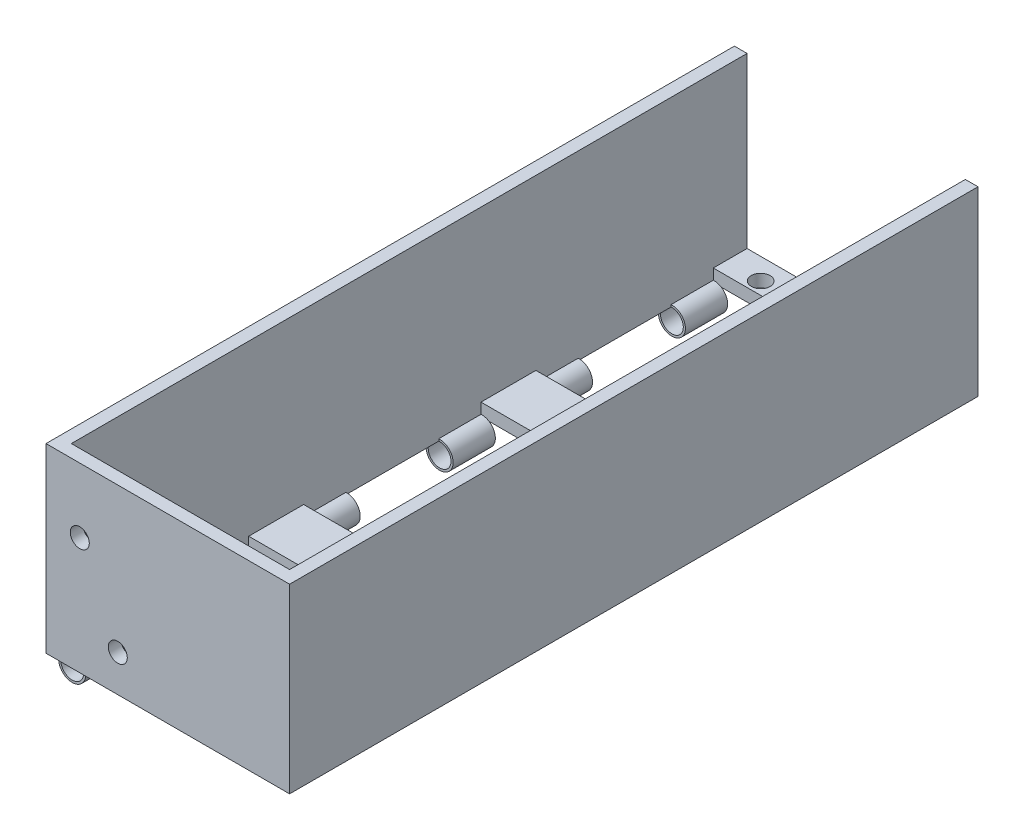
SolidWorks part; units mm, degrees
ref_plane "Front Plane" through (0, 0, 0) normal (0, 0, 1) x (1, 0, 0)
ref_plane "Top Plane" through (0, 0, 0) normal (0, 1, 0) x (1, 0, 0)
ref_plane "Right Plane" through (0, 0, 0) normal (1, 0, 0) x (0, 0, -1)
sketch "Sketch1" plane through (0, 0, 0) normal (0, 0, 1) x (1, 0, 0)
  line L0 (0, 0) -> (0, -10)
  line L1 (0, -10) -> (0, -40)
  line L2 (0, -40) -> (51.6786, -40)
  line L5 (-3, 0) -> (-3, -10)
  line L6 (-3, -10) -> (-3, -43)
  line L7 (-3, -43) -> (54.6786, -43)
  line L10 (-3, 0) -> (0, 0)
  line L12 (51.6786, -40) -> (51.6786, 0)
  line L13 (51.6786, -40) -> (51.6786, 37.6119) construction
  line L14 (51.6786, 37.6119) -> (67.0297, -2.1736) construction
  line L15 (54.6786, -43) -> (54.6786, 21.503) construction
  line L16 (54.6786, 21.503) -> (64.2308, -3.2535) construction
  line L17 (51.6786, 0) -> (54.6786, 0)
  line L18 (54.6786, 0) -> (54.6786, -43)
  dimension "D2" = 10
  dimension "D3" = 30
  dimension "D5" = 3
  dimension "D1" = 3
extrude "Boss-Extrude1" add sketch "Sketch1" along normal blind 160
sketch "Sketch2" plane through (0, 0, 0) normal (0, 1, 0) x (1, 0, 0)
  line L0 (51.6786, -160) -> (0, -160) construction
  line L1 (49, -8) -> (0, -8)
  line L2 (49, -8) -> (49, -50)
  line L3 (49, -50) -> (0, -50)
  line L4 (0, -8) -> (0, -50)
  line L5 (49, -63) -> (0, -63)
  line L6 (49, -63) -> (49, -105)
  line L7 (49, -105) -> (0, -105)
  line L8 (0, -63) -> (0, -105)
  line L9 (49, -118) -> (0, -118)
  line L10 (49, -118) -> (49, -160)
  line L11 (49, -160) -> (0, -160)
  line L12 (0, -118) -> (0, -160)
  line L13 (0, -160) -> (0, 0) construction
  dimension "D1" = 42
  dimension "D2" = 13
  dimension "D3" = 42
  dimension "D4" = 13
  dimension "D5" = 42
  dimension "D6" = 49
extrude "Cut-Extrude1" cut sketch "Sketch2" against normal through all
sketch "Sketch3" plane through (0, 0, 160) normal (0, 0, 1) x (1, 0, 0)
  line L0 (-3, 0) -> (54.6786, 0)
  line L1 (54.6786, 0) -> (54.6786, -43)
  line L2 (54.6786, -43) -> (0, -43)
  line L10 (0, 0) -> (-3, 0)
  line L11 (-3, 0) -> (-3, -43)
  line L13 (-3, -43) -> (0, -43)
  line L18 (0, -43) -> (0, 0)
  line L21 (-3, 0) -> (-3, -43)
  line L23 (-3, -43) -> (0, -43)
  dimension "D1" = 0
extrude "Boss-Extrude2" add sketch "Sketch3" along normal blind 3
sketch "Sketch4" plane through (0, 0, 163) normal (0, 0, 1) x (1, 0, 0)
  circle A0 centre (14, -34.2995) radius 2.25 construction
  circle A1 centre (5, -15.3106) radius 2.25 construction
  circle A2 centre (14, -34.2995) radius 2.25
  circle A3 centre (5, -15.3106) radius 2.25
extrude "Cut-Extrude2" cut sketch "Sketch4" against normal up to next
sketch "Sketch5" plane through (0, -40, 0) normal (0, 1, 0) x (1, 0, 0)
  line L14 (49, -8) -> (49, -50)
  line L15 (49, -50) -> (0, -50)
  line L16 (0, -50) -> (0, -63)
  line L17 (0, -63) -> (49, -63)
  line L18 (49, -63) -> (49, -105)
  line L19 (49, -105) -> (0, -105)
  line L20 (0, -105) -> (0, -118)
  line L21 (0, -118) -> (49, -118)
  line L22 (49, -118) -> (49, -160)
  line L23 (49, -160) -> (51.6786, -160)
  line L24 (51.6786, -160) -> (51.6786, 0)
  line L25 (51.6786, 0) -> (0, 0)
  line L26 (0, 0) -> (0, -8)
  line L27 (0, -8) -> (49, -8)
  line L28 (49, -8) -> (49, -50)
  line L29 (49, -50) -> (0, -50)
  line L30 (0, -50) -> (0, -63)
  line L31 (0, -63) -> (49, -63)
  line L32 (49, -63) -> (49, -105)
  line L33 (49, -105) -> (0, -105)
  line L34 (0, -105) -> (0, -118)
  line L35 (0, -118) -> (49, -118)
  line L36 (49, -118) -> (49, -160)
  line L37 (49, -160) -> (51.6786, -160)
  line L38 (51.6786, -160) -> (51.6786, 0)
  line L39 (51.6786, 0) -> (0, 0)
  line L40 (0, 0) -> (0, -8)
  line L41 (0, -8) -> (49, -8)
  ellipse E0 centre (8.2809, -5.054) end of major axis (6.0309, -5.054) minor radius 2.2278 construction
  ellipse E1 centre (8.2809, -5.054) end of major axis (6.0309, -5.054) minor radius 2.2278
  dimension "D1" = 0
extrude "Cut-Extrude3" cut sketch "Sketch5" against normal up to next contours E1 region at (8.2809, -40, 5.054)
sketch "Sketch6" plane through (0, 0, 160) normal (0, 0, 1) x (1, 0, 0)
  line L0 (-3, 0) -> (-3, -43) construction
  line L4 (6.0309, -43) -> (10.5309, -43) construction
  circle A0 centre (0.2, -45.7) radius 2.7
  circle A1 centre (0.2, -45.7) radius 3.2
  dimension "D1" = 6.4
  dimension "D2" = 5.4
extrude "Boss-Extrude3" add sketch "Sketch6" against normal blind 10
pattern_linear "LPattern1" count 3 spacing 55 along (0, 0, -1) of "Boss-Extrude3"
sketch "Sketch8" plane through (0, 0, 118) normal (0, 0, 1) x (1, 0, 0)
  circle A0 centre (0.2, -45.7) radius 2.7 construction
  arc A1 (-1.5176, -43) -> (0, -42.5063) centre (0.2, -45.7) ccw construction
  circle A2 centre (0.2, -45.7) radius 2.7
  circle A3 centre (0.2, -45.7) radius 3.2
extrude "Boss-Extrude5" add sketch "Sketch8" along normal blind 10
pattern_linear "LPattern4" count 3 spacing 55 along (0, 0, -1) of "Boss-Extrude5"
sketch "Sketch9" plane through (0, -43, 0) normal (0, -1, 0) x (1, 0, 0)
  line L0 (-3, 163) -> (-3, 0) construction
  line L1 (-1.5176, 160) -> (-3, 160)
  line L2 (-1.5176, 160) -> (-1.5176, 150)
  line L3 (-1.5176, 150) -> (-3, 150)
  line L4 (-3, 160) -> (-3, 150)
  line L5 (-3, 150) -> (3.4, 150) construction
  line L6 (-3, 118) -> (3.4, 118) construction
  line L7 (-1.5176, 105) -> (-3, 105)
  line L8 (-1.5176, 105) -> (-1.5176, 95)
  line L9 (-1.5176, 95) -> (-3, 95)
  line L10 (-3, 105) -> (-3, 95)
  line L11 (-1.5176, 128) -> (-3, 128)
  line L12 (-1.5176, 128) -> (-1.5176, 118)
  line L13 (-1.5176, 118) -> (-3, 118)
  line L14 (-3, 128) -> (-3, 118)
  line L15 (-1.5176, 73) -> (-3, 73)
  line L16 (-1.5176, 73) -> (-1.5176, 63)
  line L17 (-1.5176, 63) -> (-3, 63)
  line L18 (-3, 73) -> (-3, 63)
  line L19 (-1.5176, 50) -> (-3, 50)
  line L20 (-1.5176, 50) -> (-1.5176, 40)
  line L21 (-1.5176, 40) -> (-3, 40)
  line L22 (-3, 50) -> (-3, 40)
  line L23 (-1.5176, 18) -> (-3, 18)
  line L24 (-1.5176, 18) -> (-1.5176, 8)
  line L25 (-1.5176, 8) -> (-3, 8)
  line L26 (-3, 18) -> (-3, 8)
  line L27 (-3, 95) -> (3.4, 95) construction
  line L28 (-3, 63) -> (3.4, 63) construction
  line L29 (-3, 40) -> (3.4, 40) construction
extrude "Boss-Extrude6" add sketch "Sketch9" along normal up to next
sketch "Sketch10" plane through (-3, 0, 0) normal (-1, 0, 0) x (0, 0, 1)
  line L0 (128, -45.7) -> (128, -43) construction
  line L1 (122.4, -43) -> (125.4, -43)
  line L2 (122.4, -43) -> (122.4, -48)
  line L3 (122.4, -48) -> (125.4, -48)
  line L4 (125.4, -43) -> (125.4, -48)
  line L5 (122.4, -15.4) -> (125.4, -15.4)
  line L6 (122.4, -15.4) -> (122.4, -20.4)
  line L7 (122.4, -20.4) -> (125.4, -20.4)
  line L8 (125.4, -15.4) -> (125.4, -20.4)
  line L9 (150, -43) -> (128, -43) construction
  dimension "D1" = 2.6
  dimension "D2" = 22.6
  dimension "D3" = 5
  dimension "D4" = 5
  dimension "D5" = 3
  dimension "D6" = 3
extrude "Boss-Extrude7" add sketch "Sketch10" along normal blind 13
pattern_linear "LPattern5" count 3 spacing 55 along (0, 0, -1) of "Boss-Extrude7"
sketch "Sketch11" plane through (0, 0, 125.4) normal (0, 0, 1) x (1, 0, 0)
  circle A0 centre (-9.2, -45.95) radius 1
  circle A1 centre (-9.2, -17.45) radius 1
  dimension "D1" = 2
extrude "Cut-Extrude4" cut sketch "Sketch11" against normal through all
fillet "Fillet1" radius 4 9 edges at (-3, -15.4, 123.9) (-3, -17.9, 122.4) (-3, -44.35, 122.4) (-3, -44.35, 12.4) (-3, -17.9, 12.4) (-3, -15.4, 13.9) (-3, -44.35, 67.4) (-3, -15.4, 68.9) (-3, -17.9, 67.4)
